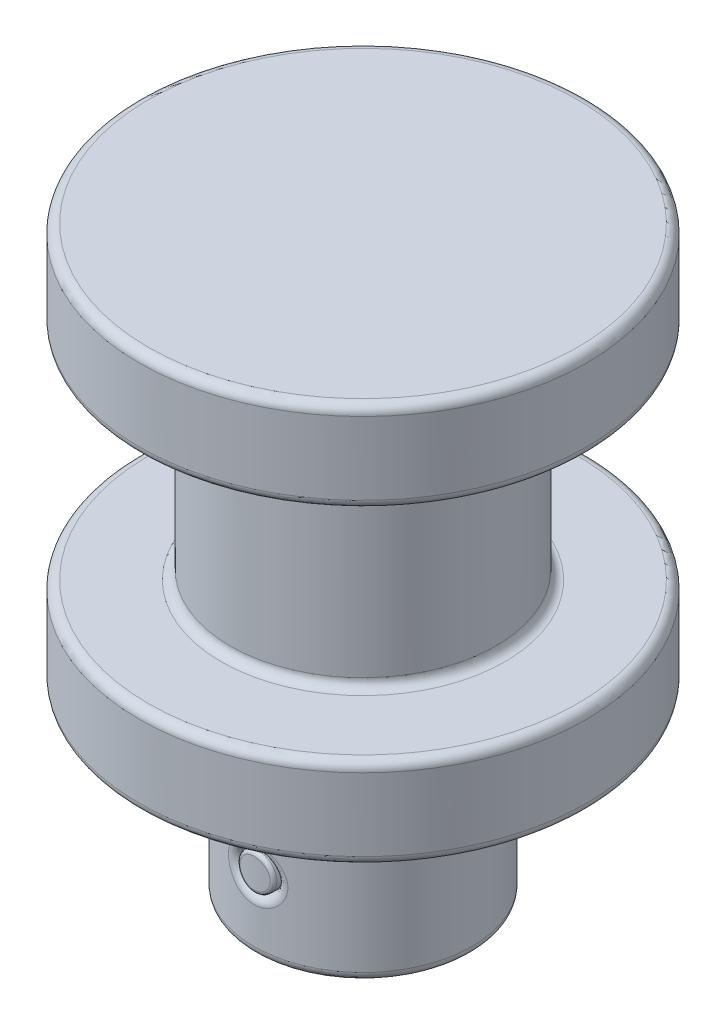
SolidWorks part; units mm, degrees
ref_plane "Front Plane" through (0, 0, 0) normal (0, 0, 1) x (1, 0, 0)
ref_plane "Top Plane" through (0, 0, 0) normal (0, 1, 0) x (1, 0, 0)
ref_plane "Right Plane" through (0, 0, 0) normal (1, 0, 0) x (0, 0, -1)
sketch "Sketch2" plane through (0, 0, 0) normal (0, 0, 1) x (1, 0, 0)
  line L0 (0, 0) -> (0, 103.7023) construction
  line L1 (0, 8) -> (5, 8)
  line L2 (5, 8) -> (5, 0)
  line L3 (5, 0) -> (6, 0)
  line L4 (6, 0) -> (6, 10)
  line L5 (6, 10) -> (12.3199, 10)
  line L6 (12.3199, 10) -> (12.3199, 15)
  line L7 (12.3199, 15) -> (7.3199, 15)
  line L8 (7.3199, 15) -> (7.3199, 27)
  line L9 (7.3199, 27) -> (12.3199, 27)
  line L10 (12.3199, 27) -> (12.3199, 32)
  line L11 (12.3199, 32) -> (0, 32)
  line L12 (0, 32) -> (0, 8)
  dimension "D1" = 5
  dimension "D2" = 8
  dimension "D3" = 1
  dimension "D4" = 10
  dimension "D5" = 5
  dimension "D6" = 5
  dimension "D7" = 12
  dimension "D8" = 5
  dimension "D9" = 5
revolve "Revolve1" add sketch "Sketch2" angle 360 about L0
sketch "Sketch3" plane through (0, 0, 0) normal (0, 0, 1) x (1, 0, 0)
  line L0 (0, 0) -> (0, 10) construction
  line L1 (-6, 10) -> (6, 10) construction
  line L2 (-6, 0) -> (6, 0) construction
  circle A0 centre (0, 4) radius 1
  dimension "D1" = 4
extrude "Cut-Extrude3" cut sketch "Sketch3" against normal through all both and the other way through all
fillet "Fillet1" radius 0.5 11 edges at (0, 0, -5) (0, 0, -6) (0, 10, -6) (-0.2145, 3.0233, -5.9962) (-0.9767, 3.7855, 5.92) (0, 15, -7.3199) (0, 27, -7.3199) (0, 10, -12.3199) (0, 15, -12.3199) (0, 27, -12.3199) (0, 32, -12.3199)
sketch "Sketch4" plane through (0, 0, 0) normal (0, 0, 1) x (1, 0, 0)
  circle A0 centre (0, 4) radius 1
extrude "Boss-Extrude1" add sketch "Sketch4" along normal up to surface and the other way up to surface up to face at (0, 0.5, -6) other way up to face at (0, 0.5, -6)
fillet "Fillet2" radius 0.2 2 edges at (-0.9767, 3.7855, -5.92) (0.9767, 4.2145, 5.92)
